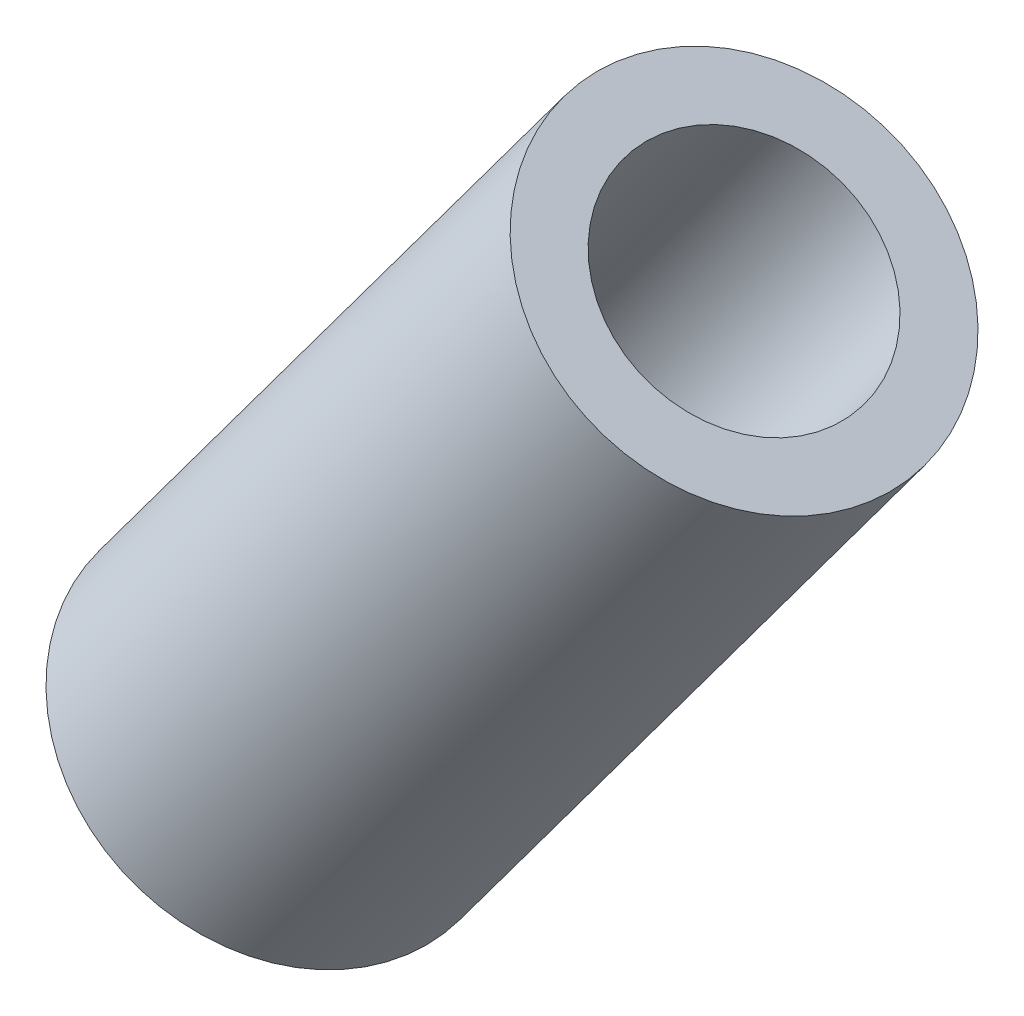
SolidWorks part; units mm, degrees
material "Silicon Rubber"
ref_plane "X-Y Datum" through (0, 0, 0) normal (0, 0, 1) x (1, 0, 0)
ref_plane "X-Z Datum" through (0, 0, 0) normal (0, 1, 0) x (1, 0, 0)
ref_plane "Y-Z Datum" through (0, 0, 0) normal (1, 0, 0) x (0, 0, -1)
sketch3d "3DSketch1"
  line L0 (0, 0, 0) -> (30.2901, 40.7817, 0)
  dimension "D1" = 50.8
sweep "Sweep1" add path "3DSketch1" circular profile diameter 23.8125 parameters "D3"=23.8125
sweep "Cut-Sweep1" cut path "3DSketch1<2>" circular profile diameter 15.875 parameters "D3"=15.875
sketch3d "3DSketch1<2>" same geometry as "3DSketch1"
sketch3d "3DSketch2"
  line L0 (0, 0, 0) -> (30.2901, 40.7817, 0) construction
  circle A1 centre (15.1451, 20.3909, 0) radius 7.9375 construction
  circle A4 centre (30.2901, 40.7817, 0) radius 7.9375 construction
  point P4 (10.4122, 14.0187, 0)
  point P8 (25.5573, 34.4096, 0)
